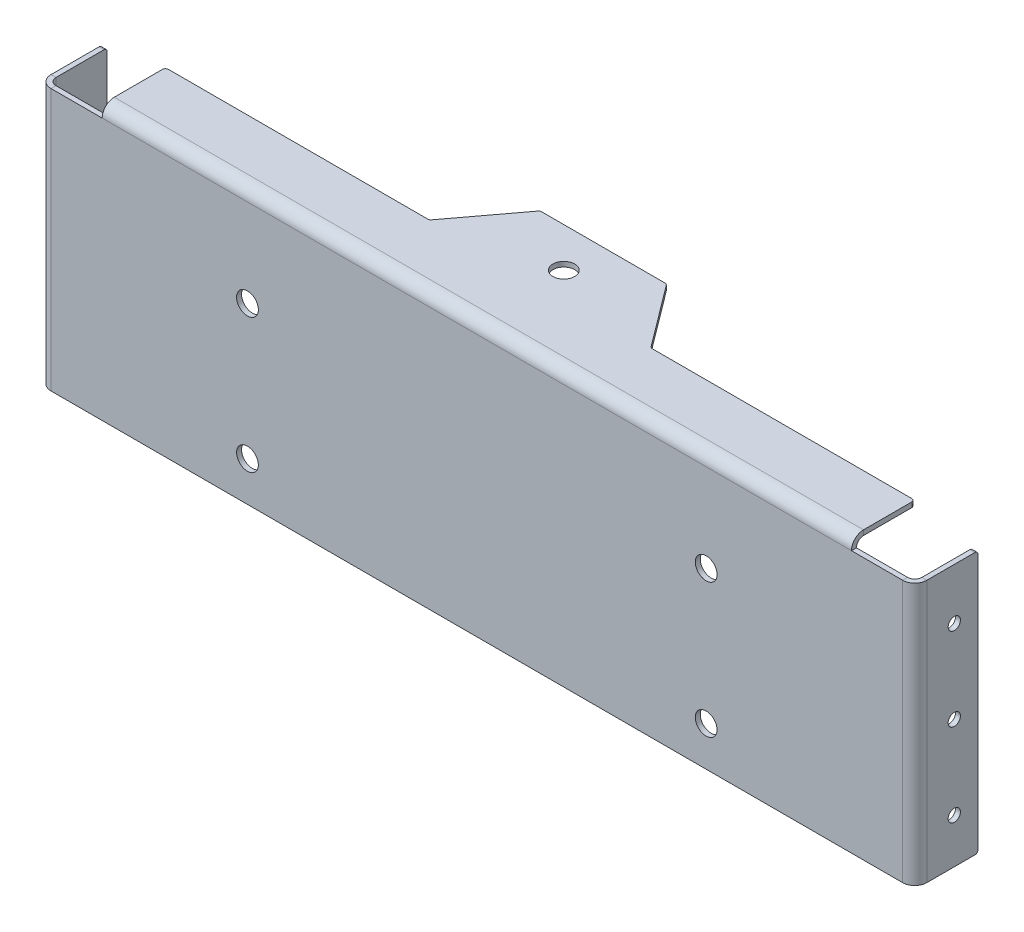
SolidWorks part; units mm, degrees
note: The reader was unsure of these and kept them because the rebuilt part matched: thickness of "Base-Flange1", "Edge-Flange1", "Edge-Flange2", "Sheet-Metal1", "Sheet-Metal2", "Sheet-Metal3", "Sheet-Metal4", "Sheet-Metal5", "Sheet-Metal6"; flange length of "Edge-Flange1", "Edge-Flange2".
material "Plain Carbon Steel"
ref_plane "Front Plane" through (0, 0, 0) normal (0, 0, 1) x (1, 0, 0)
ref_plane "Top Plane" through (0, 0, 0) normal (0, 1, 0) x (1, 0, 0)
ref_plane "Right Plane" through (0, 0, 0) normal (1, 0, 0) x (0, 0, -1)
sketch "Sketch1" plane through (0, 0, 0) normal (0, 0, 1) x (1, 0, 0)
  line L1 (0, 0) -> (351.6122, 0)
  line L2 (0, 0) -> (0, 105.156)
  line L3 (0, 105.156) -> (351.6122, 105.156)
  line L4 (351.6122, 0) -> (351.6122, 105.156)
  dimension "D1" = 351.6122
  dimension "D2" = 105.156
base flange "Base-Flange1" sketch "Sketch1" thickness 1.9939 reverse thickness direction no parameters "D1"=2.8461
edge flange "Edge-Flange1" sketch "Sketch10" flange profiles "Sketch10", "Sketch11" flange angle 90 flange length 25.4 flange position material inside bend radius 2.8461 thickness 1.9939 relief rectangular parameters "D6"=10, "D8"=4.064
sketch "Sketch10" plane through (0, 0, -1.9939) normal (-1, 0, 0) x (0, 1, 0)
  line L0 (105.156, 0) -> (0, 0) construction
  line L1 (105.156, 0) -> (0, 0)
  line L2 (0, 0) -> (0, 23.4061)
  line L3 (0, 23.4061) -> (105.156, 23.4061)
  line L4 (105.156, 23.4061) -> (105.156, 0)
sketch "Sketch11" plane through (351.6122, 0, -1.9939) normal (1, 0, 0) x (0, -1, 0)
  line L0 (0, 0) -> (-105.156, 0) construction
  line L1 (0, 0) -> (-105.156, 0)
  line L2 (-105.156, 0) -> (-105.156, 23.4061)
  line L3 (-105.156, 23.4061) -> (0, 23.4061)
  line L4 (0, 23.4061) -> (0, 0)
bend "EdgeBend1" bend radius 2.8461 bend angle 90 parameters "D5"=1
bend "EdgeBend2" bend radius 2.8461 bend angle 90 parameters "D5"=2
edge flange "Edge-Flange2" sketch "Sketch14" flange angle 90 flange length 50.8 flange position bend outside bend radius 2.8461 thickness 1.9939 relief rectangular parameters "D6"=10
sketch "Sketch14" plane through (0, 105.156, -1.9939) normal (0, 1, 0) x (1, 0, 0)
  line L1 (326.2122, 0) -> (25.4, 0)
  line L2 (25.4, 0) -> (25.4, 23.4061)
  line L4 (326.2122, 23.4061) -> (326.2122, 0)
  line L5 (346.7722, 0) -> (4.84, 0) construction
  line L6 (0, 2.8461) -> (0, 23.4061) construction
  line L7 (25.4, 23.4061) -> (131.3561, 23.4061)
  line L8 (131.3561, 23.4061) -> (150.4061, 48.8061)
  line L9 (150.4061, 48.8061) -> (201.2061, 48.8061)
  line L10 (201.2061, 48.8061) -> (220.2561, 23.4061)
  line L11 (220.2561, 23.4061) -> (326.2122, 23.4061)
  line L12 (175.8061, 0) -> (175.8061, 48.8061) construction
  line L13 (346.7722, -1.9939) -> (4.84, -1.9939) construction
  point P4 (175.8061, 0)
  dimension "D1" = 25.4
  dimension "D2" = 25.4
  dimension "D3" = 19.05
  dimension "D4" = 25.4
  dimension "D5" = 50.8
bend "EdgeBend3" bend radius 2.8461 bend angle 90 parameters "D5"=3
hole_wizard " (0.221) Diameter Hole1" positions "Sketch15" profile "Sketch16" hole size "#10" standard "ANSI Inch" end condition through all
sketch "Sketch15" plane through (351.6122, 0, 0) normal (1, 0, 0) x (0, 0, -1)
  line L0 (0, 0) -> (0, 105.156) construction
  line L2 (15.875, 17.921) -> (15.875, 84.596) construction
  line L3 (25.4, 109.996) -> (4.84, 109.996) construction
  point P1 (15.875, 84.596)
  point P3 (15.875, 17.921)
  point P11 (15.875, 51.2585)
  dimension "D1" = 15.875
  dimension "D2" = 25.4
  dimension "D3" = 66.675
sketch "Sketch16" plane through (351.6122, 84.596, -15.875) normal (0, 1, 0) x (0, 0, -1)
  line L0 (0, 0) -> (0, 351.6122)
  line L1 (0, 351.6122) -> (2.4574, 351.6122)
  line L2 (2.4574, 351.6122) -> (2.4574, 0)
  line L5 (2.4574, 0) -> (0, 0)
  line L11 (0, -6.35) -> (0, 107.95) construction
  dimension "Thru Hole Dia." = 4.9149
  dimension "Thru Hole Depth" = 351.6122
hole_wizard "Hole for 1/4 Self-clinching Nuts (S,SS,CLS,CLSS)1" positions "Sketch17" profile "Sketch18" hole size "1/4-20" standard "PEM® Inch" end condition through all
sketch "Sketch17" plane through (0, 109.996, 0) normal (0, 1, 0) x (1, 0, 0)
  line L0 (201.2061, 50.8) -> (150.4061, 50.8) construction
  line L1 (175.8061, 50.8) -> (175.8061, 0) construction
  line L2 (326.2122, 0) -> (25.4, 0) construction
  line L3 (0, 177.8) -> (351.6122, 177.8) construction
  line L4 (351.6122, 25.4) -> (351.6122, 4.84) construction
  line L5 (0, 4.84) -> (0, 25.4) construction
  point P0 (175.8061, 34.925)
  dimension "D1" = 177.8
  dimension "D2" = 142.875
  dimension "D3" = 15.875
sketch "Sketch18" plane through (175.8061, 109.996, -34.925) normal (1, 0, 0) x (0, 0, 1)
  line L0 (0, 0) -> (0, 109.996)
  line L1 (0, 109.996) -> (4.3688, 109.996)
  line L2 (4.3688, 109.996) -> (4.3688, 0)
  line L5 (4.3688, 0) -> (0, 0)
  line L11 (0, -6.35) -> (0, 107.95) construction
  dimension "Thru Hole Dia." = 8.7376
  dimension "Thru Hole Depth" = 109.996
hole_wizard "Hole for 1/4 Self-clinching Nuts (S,SS,CLS,CLSS)2" positions "Sketch19" profile "Sketch20" hole size "1/4-20" standard "PEM® Inch" end condition through all
sketch "Sketch19" plane through (0, 0, 0) normal (0, 0, 1) x (1, 0, 0)
  line L0 (175.8061, 0) -> (175.8061, 109.996) construction
  line L1 (4.84, 0) -> (346.7722, 0) construction
  line L2 (326.2122, 109.996) -> (25.4, 109.996) construction
  line L3 (125.0061, 0) -> (125.0061, 109.996) construction
  point P0 (83.7311, 69.864)
  point P2 (83.7311, 15.889)
  point P17 (267.8811, 15.889)
  point P18 (267.8811, 69.864)
  dimension "D1" = 50.8
  dimension "D2" = 40.132
  dimension "D3" = 53.975
  dimension "D4" = 92.075
sketch "Sketch20" plane through (83.7311, 69.864, 0) normal (1, 0, 0) x (0, -1, 0)
  line L0 (0, 0) -> (0, 50.8)
  line L1 (0, 50.8) -> (4.3688, 50.8)
  line L2 (4.3688, 50.8) -> (4.3688, 0)
  line L5 (4.3688, 0) -> (0, 0)
  line L11 (0, -6.35) -> (0, 107.95) construction
  dimension "Thru Hole Dia." = 8.7376
  dimension "Thru Hole Depth" = 50.8
fillet "Fillet1" radius 1.27 10 edges at (350.6153, 0, -25.4) (350.6153, 105.156, -25.4) (0.9969, 0, -25.4) (0.9969, 105.156, -25.4) (326.2122, 108.999, -25.4) (220.2561, 108.999, -25.4) (201.2061, 108.999, -50.8) (150.4061, 108.999, -50.8) (131.3561, 108.999, -25.4) (25.4, 108.999, -25.4)
sketch "Bend-Lines1" [suppressed] plane through (0, 0, 0) normal (0, 1, 0) x (1, 0, 0)
sketch "Bounding-Box1" [suppressed] plane through (0, 0, 0) normal (0, 1, 0) x (1, 0, 0)
sheet metal parameters "Sheet-Metal1" thickness 1.9939 parameters "D1"=2.8461, "D7"=1.8974
flat pattern "Flat-Pattern1" [suppressed]
sketch "Bend-Lines2" plane through (0, 0, 0) normal (0, 1, 0) x (1, 0, 0)
sketch3d "Bounding-Box2" [suppressed]
  line L0 (0, 0, 0) -> (-381, 0, 0) construction
  line L1 (0, 63.5, 0) -> (-381, 63.5, 0) construction
  line L2 (0, 0, 0) -> (0, 63.5, 0) construction
  line L3 (-381, 0, 0) -> (-381, 63.5, 0) construction
sheet metal parameters "Sheet-Metal2" thickness 1.9939 parameters "D1"=2.8461, "D7"=1.8974
flat pattern "Flat-Pattern1"
sketch "Bend-Lines2" plane through (0, 0, 0) normal (0, 0, 1) x (1, 0, 0)
  line L0 (383.9804, 0) -> (383.9804, 63.5) construction
  line L1 (-2.9804, 63.5) -> (-2.9804, 0) construction
  line L2 (383.9804, 0) -> (383.9804, 63.5) construction
  line L3 (-2.9804, 63.5) -> (-2.9804, 0) construction
sketch3d "Bounding-Box2" [suppressed]
  line L0 (-26.6173, 0, 0) -> (407.6173, 0, 0) construction
  line L1 (-26.6173, 63.5, 0) -> (407.6173, 63.5, 0) construction
  line L2 (-26.6173, 0, 0) -> (-26.6173, 63.5, 0) construction
  line L3 (407.6173, 0, 0) -> (407.6173, 63.5, 0) construction
bend of the flat pattern "Flatten-<EdgeBend1>1"
bend of the flat pattern "Flatten-<EdgeBend2>1"
sheet metal parameters "Sheet-Metal3" thickness 1.9939 parameters "D1"=2.8461, "D7"=1.8974
flat pattern "Flat-Pattern1"
sketch "Bend-Lines2" plane through (0, 0, 0) normal (0, 0, 1) x (1, 0, 0)
  line L0 (375.4269, 0) -> (375.4269, 63.5) construction
  line L1 (1.7631, 63.5) -> (1.7631, 0) construction
  line L2 (375.4269, 0) -> (375.4269, 63.5) construction
  line L3 (1.7631, 63.5) -> (1.7631, 0) construction
  line L4 (351.79, 66.4804) -> (25.4, 66.4804) construction
  line L5 (351.79, 66.4804) -> (25.4, 66.4804) construction
sketch3d "Bounding-Box2" [suppressed]
  line L0 (-21.8739, 0, 0) -> (399.0639, 0, 0) construction
  line L1 (-21.8739, 115.5173, 0) -> (399.0639, 115.5173, 0) construction
  line L2 (-21.8739, 0, 0) -> (-21.8739, 115.5173, 0) construction
  line L3 (399.0639, 0, 0) -> (399.0639, 115.5173, 0) construction
bend of the flat pattern "Flatten-<EdgeBend1>1"
bend of the flat pattern "Flatten-<EdgeBend2>1"
bend of the flat pattern "Flatten-<EdgeBend3>1"
sheet metal parameters "Sheet-Metal4" thickness 1.9939 parameters "D1"=2.8461, "D7"=1.8974
flat pattern "Flat-Pattern1"
sketch "Bend-Lines2" plane through (0, 0, 0) normal (0, 0, 1) x (1, 0, 0)
  line L0 (375.4269, 0) -> (375.4269, 63.5) construction
  line L1 (1.7631, 63.5) -> (1.7631, 0) construction
  line L2 (375.4269, 0) -> (375.4269, 63.5) construction
  line L3 (1.7631, 63.5) -> (1.7631, 0) construction
  line L4 (351.79, 66.4804) -> (25.4, 66.4804) construction
  line L5 (351.79, 66.4804) -> (25.4, 66.4804) construction
sketch3d "Bounding-Box2" [suppressed]
  line L0 (-21.8739, 0, 0) -> (399.0639, 0, 0) construction
  line L1 (-21.8739, 115.5173, 0) -> (399.0639, 115.5173, 0) construction
  line L2 (-21.8739, 0, 0) -> (-21.8739, 115.5173, 0) construction
  line L3 (399.0639, 0, 0) -> (399.0639, 115.5173, 0) construction
bend of the flat pattern "Flatten-<EdgeBend1>1"
bend of the flat pattern "Flatten-<EdgeBend2>1"
bend of the flat pattern "Flatten-<EdgeBend3>1"
sheet metal parameters "Sheet-Metal5" thickness 1.9939 parameters "D1"=2.8461, "D7"=1.8974
flat pattern "Flat-Pattern1"
sketch "Bend-Lines2" plane through (0, 0, 0) normal (0, 0, 1) x (1, 0, 0)
  line L0 (350.0422, 0) -> (350.0422, 82.55) construction
  line L1 (1.7631, 82.55) -> (1.7631, 0) construction
  line L2 (350.0422, 0) -> (350.0422, 82.55) construction
  line L3 (1.7631, 82.55) -> (1.7631, 0) construction
  line L4 (326.4052, 85.5304) -> (25.4, 85.5304) construction
  line L5 (326.4052, 85.5304) -> (25.4, 85.5304) construction
sketch3d "Bounding-Box2" [suppressed]
  line L0 (-21.8739, 0, 0) -> (373.6791, 0, 0) construction
  line L1 (-21.8739, 134.5673, 0) -> (373.6791, 134.5673, 0) construction
  line L2 (-21.8739, 0, 0) -> (-21.8739, 134.5673, 0) construction
  line L3 (373.6791, 0, 0) -> (373.6791, 134.5673, 0) construction
bend of the flat pattern "Flatten-<EdgeBend1>1"
bend of the flat pattern "Flatten-<EdgeBend2>1"
bend of the flat pattern "Flatten-<EdgeBend3>1"
sheet metal parameters "Sheet-Metal6" thickness 1.9939 parameters "D1"=2.8461, "D7"=1.8974
flat pattern "Flat-Pattern1"
sketch "Bend-Lines2" plane through (0, 0, 0) normal (0, 0, 1) x (1, 0, 0)
  line L0 (349.7905, 0) -> (349.7905, 105.156) construction
  line L1 (1.8217, 105.156) -> (1.8217, 0) construction
  line L2 (349.7905, 0) -> (349.7905, 105.156) construction
  line L3 (1.8217, 105.156) -> (1.8217, 0) construction
  line L4 (326.2122, 108.1743) -> (25.4, 108.1743) construction
  line L5 (326.2122, 108.1743) -> (25.4, 108.1743) construction
sketch3d "Bounding-Box2" [suppressed]
  line L0 (-21.7567, 0, 0) -> (373.3689, 0, 0) construction
  line L1 (-21.7567, 157.1526, 0) -> (373.3689, 157.1526, 0) construction
  line L2 (-21.7567, 0, 0) -> (-21.7567, 157.1526, 0) construction
  line L3 (373.3689, 0, 0) -> (373.3689, 157.1526, 0) construction
bend of the flat pattern "Flatten-<EdgeBend1>1"
bend of the flat pattern "Flatten-<EdgeBend2>1"
bend of the flat pattern "Flatten-<EdgeBend3>1"
equation "\"D1@Sketch1\"=14-2*\"Thickness\""
